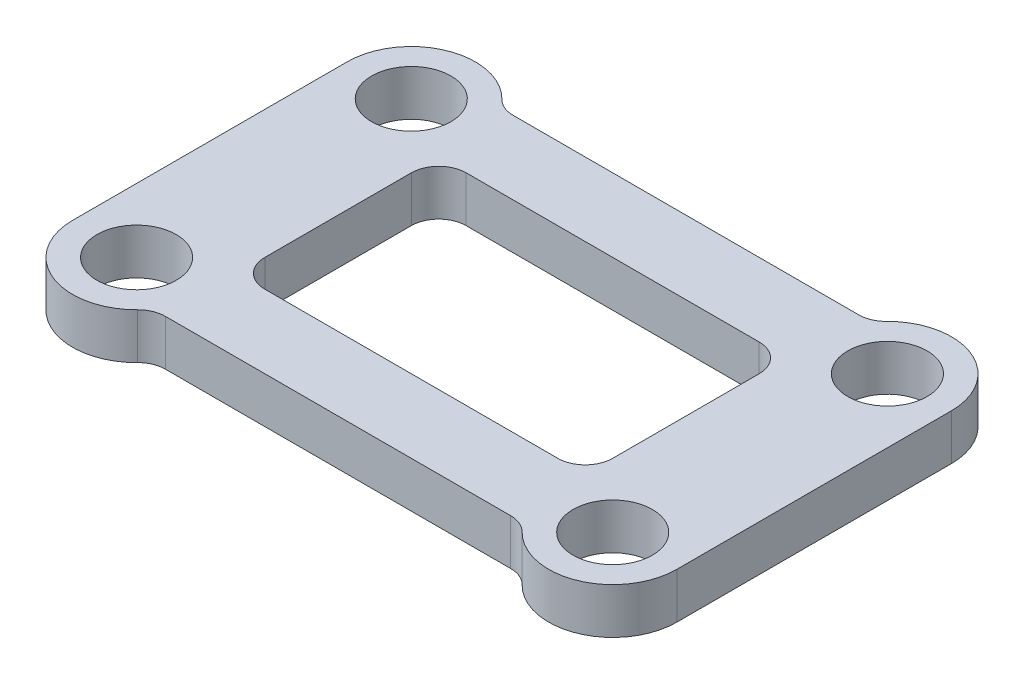
SolidWorks part; units mm, degrees
material "6061-T6 (SS)"
ref_plane "Front Plane" through (0, 0, 0) normal (0, 0, 1) x (1, 0, 0)
ref_plane "Top Plane" through (0, 0, 0) normal (0, 1, 0) x (1, 0, 0)
ref_plane "Right Plane" through (0, 0, 0) normal (1, 0, 0) x (0, 0, -1)
sketch "Sketch1" plane through (0, -19.05, 0) normal (0, -1, 0) x (1, 0, 0)
  line L0 (-29.21, 9.525) -> (-29.21, -9.525) construction
  line L5 (-24.765, 9.525) -> (-24.765, -9.525)
  line L6 (-33.655, 9.525) -> (-33.655, -9.525)
  line L7 (3.81, 9.525) -> (3.81, -9.525) construction
  line L8 (8.255, 9.525) -> (8.255, -9.525)
  line L9 (-0.635, 9.525) -> (-0.635, -9.525)
  arc A4 (-24.765, 9.525) -> (-33.655, 9.525) centre (-29.21, 9.525) ccw
  arc A5 (-33.655, -9.525) -> (-24.765, -9.525) centre (-29.21, -9.525) ccw
  arc A6 (8.255, 9.525) -> (-0.635, 9.525) centre (3.81, 9.525) ccw
  arc A7 (-0.635, -9.525) -> (8.255, -9.525) centre (3.81, -9.525) ccw
  point P2 (-29.21, 0)
  point P12 (3.81, 0)
  dimension "D1" = 4.445
  dimension "D2" = 4.445
extrude "Boss-Extrude2" add sketch "Sketch1" along normal blind 3.175
sketch "Sketch7" plane through (0, -22.225, 0) normal (0, -1, 0) x (1, 0, 0)
  line L0 (-29.21, 9.525) -> (3.81, 9.525)
  line L2 (-29.21, -9.525) -> (3.81, -9.525)
extrude "Extrude-Thin1" add sketch "Sketch7" against normal up to surface (3.175 mm away) thin up to face at (-29.21, -19.05, 0) thin type mid plane wall 5.08
hole_wizard "M5 Clearance Hole1" positions "3DSketch1" profile "Sketch5" hole size "M5" standard "ANSI Metric" end condition through all
sketch3d "3DSketch1"
  line L0 (-29.21, -22.225, 9.525) -> (-29.21, -19.05, 9.525) construction
  line L1 (-29.21, -22.225, -9.525) -> (-29.21, -19.05, -9.525) construction
  line L2 (3.81, -22.225, 9.525) -> (3.81, -19.05, 9.525) construction
  line L3 (3.81, -22.225, -9.525) -> (3.81, -19.05, -9.525) construction
  point P0 (-29.21, -22.225, 9.525)
  point P4 (-29.21, -22.225, -9.525)
  point P8 (3.81, -22.225, 9.525)
  point P12 (3.81, -22.225, -9.525)
sketch "Sketch5" plane through (-29.21, -22.225, 9.525) normal (1, 0, 0) x (0, 0, -1)
  line L0 (0, 0) -> (0, 3.175)
  line L1 (0, 3.175) -> (2.75, 3.175)
  line L2 (2.75, 3.175) -> (2.75, 0)
  line L5 (2.75, 0) -> (0, 0)
  line L11 (0, -6.35) -> (0, 107.95) construction
  dimension "Thru Hole Dia." = 5.5
  dimension "Thru Hole Depth" = 3.175
fillet "Fillet1" radius 1.905 8 edges at (-25.5622, -20.6375, -12.065) (0.1622, -20.6375, -12.065) (-0.635, -20.6375, -6.985) (-24.765, -20.6375, 6.985) (0.1622, -20.6375, 12.065) (-25.5622, -20.6375, 12.065) (-0.635, -20.6375, 6.985) (-24.765, -20.6375, -6.985)
